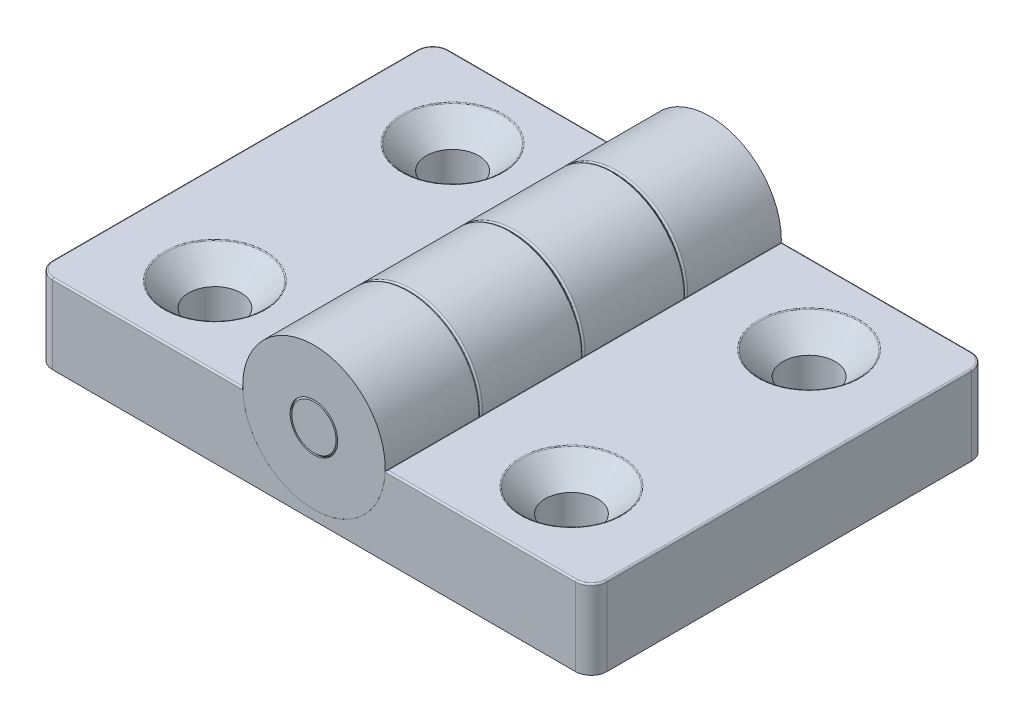
SolidWorks part; units mm, degrees
ref_plane "前视基准面" through (0, 0, 0) normal (0, 0, 1) x (1, 0, 0)
ref_plane "上视基准面" through (0, 0, 0) normal (0, 1, 0) x (1, 0, 0)
ref_plane "右视基准面" through (0, 0, 0) normal (1, 0, 0) x (0, 0, -1)
sketch "草图1" plane through (0, 0, 0) normal (0, 0, 1) x (1, 0, 0)
  circle A0 centre (0, 0) radius 9
  circle A1 centre (0, 0) radius 3
  dimension "D1" = 18
  dimension "D2" = 6
extrude "凸台-拉伸1" add sketch "草图1" along normal mid plane 50
sketch "草图2" plane through (0, 0, 0) normal (0, 0, 1) x (1, 0, 0)
  circle A0 centre (0, 0) radius 3
  dimension "D1" = 6
extrude "凸台-拉伸2" add sketch "草图2" along normal mid plane 50 separate body
chamfer "倒角1" distance 0.2 angle 45 1 edges at (3, 0, 25)
sketch "草图3" plane through (0, 0, 0) normal (0, 1, 0) x (1, 0, 0)
  line L0 (0, 0) -> (14.2235, 0) construction
  line L1 (9, 13) -> (7, 13)
  line L2 (9, 13) -> (9, 12.9)
  line L3 (9, 12.9) -> (7, 12.9)
  line L4 (7, 13) -> (7, 12.9)
  line L5 (9, 25) -> (-9, 25) construction
  line L6 (-9, -25) -> (9, -25) construction
  line L7 (9, -25) -> (9, 25) construction
  line L9 (9, 0.05) -> (7, 0.05)
  line L10 (9, 0.05) -> (9, -0.05)
  line L11 (9, -0.05) -> (7, -0.05)
  line L12 (7, 0.05) -> (7, -0.05)
  line L13 (9, -12.9) -> (4.8947, -12.9)
  line L14 (9, -12.9) -> (9, -13)
  line L15 (9, -13) -> (4.8947, -13)
  line L16 (4.8947, -12.9) -> (4.8947, -13)
  point P4 (9, 0)
  dimension "D1" = 12
  dimension "D2" = 0.1
  dimension "D3" = 12
  dimension "D4" = 2
revolve "切除-旋转1" cut sketch "草图3" angle 360 about axis through (0, 0, 25) along (0, 0, -1)
fillet "圆角1" radius 0.2 6 edges at (9, 0, 13) (9, 0, 12.9) (9, 0, 0.05) (9, 0, -0.05) (9, 0, -12.9) (9, 0, -13)
sketch "草图4" plane through (0, 0, 0) normal (0, 1, 0) x (1, 0, 0)
  line L0 (-9, -25) -> (9, -25) construction
  line L1 (-19.5, 25) -> (19.5, 25)
  line L2 (-19.5, 25) -> (-19.5, -25)
  line L3 (-19.5, -25) -> (19.5, -25)
  line L4 (19.5, 25) -> (19.5, -25)
  line L5 (9, 25) -> (-9, 25) construction
  point P4 (0, -25)
  dimension "D1" = 39
sketch "草图5" plane through (0, 0, -25) normal (0, 0, -1) x (-1, 0, 0)
  line L0 (8.9978, -0.2) -> (35, -0.2)
  line L3 (-35, -0.2) -> (-8.9978, -0.2)
  line L4 (-35, -0.2) -> (-35, -10.2)
  line L5 (-35, -10.2) -> (35, -10.2)
  line L6 (35, -0.2) -> (35, -10.2)
  circle A0 centre (0, 0) radius 9 construction
  arc A1 (-8.9978, -0.2) -> (8.9978, -0.2) centre (0, 0) ccw
  dimension "D2" = 0.2
  dimension "D4" = 35
  dimension "D1" = 10
  dimension "D3" = 70
extrude "凸台-拉伸6" add sketch "草图5" against normal up to surface (50 mm away) separate body up to face at (9, 0, 25)
hole_wizard "M6 平头机械螺钉的锥形沉头孔1" positions "草图7" profile "草图6" countersink size "M6" standard "Ansi Metric" end condition through all
sketch "草图7" plane through (0, -0.2, 0) normal (0, 1, 0) x (-1, 0, 0)
  line L0 (0, 0) -> (0, 18.3669) construction
  line L2 (0, 0) -> (27.3768, 0) construction
  point P1 (22.5, -15)
  point P3 (-22.5, -15)
  point P5 (22.5, 15)
  point P7 (-22.5, 15)
  dimension "D1" = 45
  dimension "D2" = 30
sketch "草图6" plane through (-22.5, -0.2, -15) normal (1, 0, 0) x (0, 0, 1)
  line L0 (0, 0) -> (0, 10)
  line L1 (0, 10) -> (3.3, 10)
  line L2 (3.3, 10) -> (3.3, 3)
  line L3 (3.3, 3) -> (6.3, 0)
  line L5 (6.3, 0) -> (0, 0)
  line L6 (-3.3, 3) -> (-6.3, 0) construction
  line L11 (0, -6.35) -> (0, 107.95) construction
  dimension "通孔孔直径" = 6.6
  dimension "通孔孔深度" = 10
  dimension "近端锥形沉头孔直径" = 12.6
  dimension "近端锥形沉头孔角度" = 90
fillet "圆角2" radius 0.2 12 edges at (21.9989, -0.2, -25) (35, -0.2, 0) (21.9989, -0.2, 25) (8.9978, -0.2, 0) (22.5, -0.2, 21.3) (22.5, -0.2, -8.7) (-21.9989, -0.2, -25) (-8.9978, -0.2, 0) (-21.9989, -0.2, 25) (-35, -0.2, 0) (-22.5, -0.2, 21.3) (-22.5, -0.2, -8.7)
fillet "圆角3" radius 2 8 edges at (-34.9414, -0.2586, -24.9414) (34.9414, -0.2586, -24.9414) (34.9414, -0.2586, 24.9414) (-34.9414, -0.2586, 24.9414) (-35, -5.3, 25) (35, -5.3, 25) (35, -5.3, -25) (-35, -5.3, -25)
chamfer "倒角2" distance 0.5 angle 45 1 edges at (3, 0, -25)
